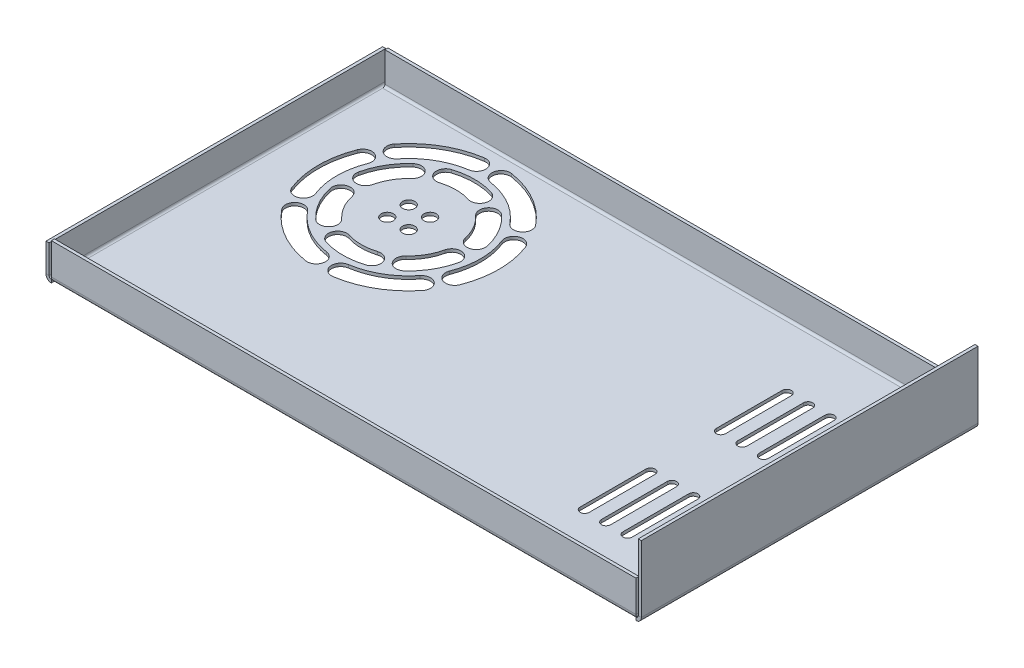
SolidWorks part; units mm, degrees
note: The reader was unsure of these and kept them because the rebuilt part matched: thickness of "Базовая кромка1", "Ребро-кромка1", "Ребро-кромка2", "Ребро-кромка3", "Ребро-кромка4", "Листовой металл3", "Листовой металл4", "Листовой металл5", "Листовой металл6", "Листовой металл7", "Листовой металл8"; flange length of "Ребро-кромка1", "Ребро-кромка2", "Ребро-кромка3", "Ребро-кромка4".
material "6063-O"
ref_plane "Спереди" through (0, 0, 0) normal (0, 0, 1) x (1, 0, 0)
ref_plane "Сверху" through (0, 0, 0) normal (0, 1, 0) x (1, 0, 0)
ref_plane "Справа" through (0, 0, 0) normal (1, 0, 0) x (0, 0, -1)
sketch "Эскиз1" plane through (0, 0, 0) normal (0, 1, 0) x (1, 0, 0)
  line L1 (-97.25, 55) -> (97.25, 55)
  line L2 (-97.25, 55) -> (-97.25, -55)
  line L3 (-97.25, -55) -> (97.25, -55)
  line L4 (97.25, 55) -> (97.25, -55)
  point P4 (0, 55)
  point P6 (-97.25, 0)
  dimension "D1" = 110
  dimension "D2" = 194.5
base flange "Базовая кромка1" sketch "Эскиз1" thickness 1 reverse thickness direction no parameters "D1"=0.7366
edge flange "Ребро-кромка1" sketch "Эскиз8" flange angle 90 flange length 23.5 flange position material inside bend radius 0.7366 thickness 1 relief rectangular parameters "D6"=10
sketch "Эскиз8" plane through (97.25, 0, 0) normal (1, 0, 0) x (0, 0, -1)
  line L0 (-55, 0) -> (55, 0) construction
  line L1 (-55, 0) -> (55, 0)
  line L2 (-55, 0) -> (-55, 22.5)
  line L3 (-55, 22.5) -> (55, 22.5)
  line L4 (55, 22.5) -> (55, 0)
bend "EdgeBend1" bend radius 0.7366 bend angle 90 parameters "D5"=1
edge flange "Ребро-кромка2" sketch "Эскиз11" flange angle 90 flange length 11 flange position material inside bend radius 0.7366 thickness 1 relief rectangular parameters "D6"=10
sketch "Эскиз11" plane through (-97.25, 0, 0) normal (-1, 0, 0) x (0, 0, 1)
  line L0 (-55, 0) -> (55, 0) construction
  line L1 (-55, 0) -> (55, 0)
  line L2 (-55, 0) -> (-55, 10)
  line L3 (-55, 10) -> (55, 10)
  line L4 (55, 10) -> (55, 0)
bend "EdgeBend2" bend radius 0.7366 bend angle 90 parameters "D5"=2
edge flange "Ребро-кромка3" sketch "Эскиз14" flange angle 90 flange length 12 flange position material inside bend radius 0.7366 thickness 1 relief none parameters "D6"=10
sketch "Эскиз14" plane through (0, 0, 55) normal (0, 0, 1) x (1, 0, 0)
  line L0 (-95.5134, 0) -> (95.5134, 0) construction
  line L1 (-95.5134, 0) -> (95.5134, 0)
  line L2 (-95.5134, 0) -> (-95.5134, 11)
  line L3 (-95.5134, 11) -> (95.5134, 11)
  line L4 (95.5134, 11) -> (95.5134, 0)
bend "EdgeBend3" bend radius 0.7366 bend angle 90 parameters "D5"=3
edge flange "Ребро-кромка4" sketch "Эскиз17" flange angle 90 flange length 11.5 flange position material inside bend radius 0.7366 thickness 1 relief none parameters "D6"=10
sketch "Эскиз17" plane through (0, 0, -55) normal (0, 0, -1) x (-1, 0, 0)
  line L0 (-95.5134, 0) -> (95.5134, 0) construction
  line L1 (-95.5134, 0) -> (95.5134, 0)
  line L2 (-95.5134, 0) -> (-95.5134, 10.5)
  line L3 (-95.5134, 10.5) -> (95.5134, 10.5)
  line L4 (95.5134, 10.5) -> (95.5134, 0)
bend "EdgeBend4" bend radius 0.7366 bend angle 90 parameters "D5"=4
sketch "Эскиз18" plane through (0, -1, 0) normal (0, -1, 0) x (1, 0, 0)
  line L0 (-95.5134, 0) -> (95.5134, 0) construction
  line L1 (-95.5134, 53.2634) -> (-95.5134, -53.2634) construction
  line L2 (95.5134, -53.2634) -> (95.5134, 53.2634) construction
  line L3 (84.75, 33) -> (84.75, 11.5) construction
  line L4 (86.25, 33) -> (86.25, 11.5)
  line L5 (83.25, 33) -> (83.25, 11.5)
  line L6 (97.25, -55) -> (97.25, 55) construction
  line L7 (95.5134, 55) -> (-95.5134, 55) construction
  line L8 (84.75, -33) -> (84.75, -11.5) construction
  line L9 (86.25, -33) -> (86.25, -11.5)
  line L10 (83.25, -33) -> (83.25, -11.5)
  line L11 (-102.5134, 0) -> (88.5134, 0) construction
  line L12 (77.75, 33) -> (77.75, 11.5) construction
  line L13 (79.25, 33) -> (79.25, 11.5)
  line L14 (76.25, 33) -> (76.25, 11.5)
  line L15 (77.75, -33) -> (77.75, -11.5) construction
  line L16 (79.25, -33) -> (79.25, -11.5)
  line L17 (76.25, -33) -> (76.25, -11.5)
  line L18 (-109.5134, 0) -> (81.5134, 0) construction
  line L19 (70.75, 33) -> (70.75, 11.5) construction
  line L20 (72.25, 33) -> (72.25, 11.5)
  line L21 (69.25, 33) -> (69.25, 11.5)
  line L22 (70.75, -33) -> (70.75, -11.5) construction
  line L23 (72.25, -33) -> (72.25, -11.5)
  line L24 (69.25, -33) -> (69.25, -11.5)
  line L25 (-116.5134, 0) -> (74.5134, 0) construction
  line L26 (63.75, 33) -> (63.75, 11.5) construction
  line L27 (65.25, 33) -> (65.25, 11.5)
  line L28 (62.25, 33) -> (62.25, 11.5)
  line L29 (63.75, -33) -> (63.75, -11.5) construction
  line L30 (65.25, -33) -> (65.25, -11.5)
  line L31 (62.25, -33) -> (62.25, -11.5)
  line L32 (-123.5134, 0) -> (67.5134, 0) construction
  line L33 (56.75, 33) -> (56.75, 11.5) construction
  line L34 (58.25, 33) -> (58.25, 11.5)
  line L35 (55.25, 33) -> (55.25, 11.5)
  line L36 (56.75, -33) -> (56.75, -11.5) construction
  line L37 (58.25, -33) -> (58.25, -11.5)
  line L38 (55.25, -33) -> (55.25, -11.5)
  line L39 (-79.4367, -30.6341) -> (-54.75, -21) construction
  line L40 (-54.75, -21) -> (-79.4367, -11.3659) construction
  line L41 (-54.75, -21) -> (-81.25, -21) construction
  line L42 (-97.25, 55) -> (-97.25, -55) construction
  line L43 (-95.5134, -55) -> (95.5134, -55) construction
  line L44 (-54.75, -21) -> (-54.75, -39.5) construction
  line L45 (-54.75, -21) -> (-75.4367, -4.4377) construction
  line L46 (-60.3171, -38.6425) -> (-54.75, -21) construction
  line L47 (-54.75, -21) -> (-49.1829, -38.6425) construction
  line L48 (-54.75, -21) -> (-67.2453, -34.6425) construction
  line L49 (-54.75, -21) -> (-70.7715, -30.25) construction
  line L50 (-72.8124, -25) -> (-54.75, -21) construction
  line L51 (-54.75, -21) -> (-67.2453, -34.6425) construction
  line L52 (-54.75, -21) -> (-72.8124, -17) construction
  line L53 (-54.75, -21) -> (-70.7715, -11.75) construction
  line L54 (-67.2453, -7.3575) -> (-54.75, -21) construction
  line L55 (-54.75, -21) -> (-72.8124, -17) construction
  line L56 (-54.75, -21) -> (-60.3171, -3.3575) construction
  line L57 (-54.75, -21) -> (-54.75, -2.5) construction
  line L58 (-49.1829, -3.3575) -> (-54.75, -21) construction
  line L59 (-54.75, -21) -> (-60.3171, -3.3575) construction
  line L60 (-54.75, -21) -> (-42.2547, -7.3575) construction
  line L61 (-54.75, -21) -> (-38.7285, -11.75) construction
  line L62 (-36.6876, -17) -> (-54.75, -21) construction
  line L63 (-54.75, -21) -> (-42.2547, -7.3575) construction
  line L64 (-54.75, -21) -> (-36.6876, -25) construction
  line L65 (-54.75, -21) -> (-38.7285, -30.25) construction
  line L66 (-42.2547, -34.6425) -> (-54.75, -21) construction
  line L67 (-54.75, -21) -> (-36.6876, -25) construction
  line L68 (-54.75, -21) -> (-49.1829, -38.6425) construction
  line L70 (-58.25, -17.5) -> (-51.25, -17.5) construction
  line L71 (-58.25, -17.5) -> (-58.25, -24.5) construction
  line L72 (-58.25, -24.5) -> (-51.25, -24.5) construction
  line L73 (-51.25, -17.5) -> (-51.25, -24.5) construction
  arc A0 (86.25, 33) -> (83.25, 33) centre (84.75, 33) ccw
  arc A1 (83.25, 11.5) -> (86.25, 11.5) centre (84.75, 11.5) ccw
  arc A2 (86.25, -33) -> (83.25, -33) centre (84.75, -33) cw
  arc A3 (83.25, -11.5) -> (86.25, -11.5) centre (84.75, -11.5) cw
  arc A4 (79.25, 33) -> (76.25, 33) centre (77.75, 33) ccw
  arc A5 (76.25, 11.5) -> (79.25, 11.5) centre (77.75, 11.5) ccw
  arc A6 (79.25, -33) -> (76.25, -33) centre (77.75, -33) cw
  arc A7 (76.25, -11.5) -> (79.25, -11.5) centre (77.75, -11.5) cw
  arc A8 (72.25, 33) -> (69.25, 33) centre (70.75, 33) ccw
  arc A9 (69.25, 11.5) -> (72.25, 11.5) centre (70.75, 11.5) ccw
  arc A10 (72.25, -33) -> (69.25, -33) centre (70.75, -33) cw
  arc A11 (69.25, -11.5) -> (72.25, -11.5) centre (70.75, -11.5) cw
  arc A12 (65.25, 33) -> (62.25, 33) centre (63.75, 33) ccw
  arc A13 (62.25, 11.5) -> (65.25, 11.5) centre (63.75, 11.5) ccw
  arc A14 (65.25, -33) -> (62.25, -33) centre (63.75, -33) cw
  arc A15 (62.25, -11.5) -> (65.25, -11.5) centre (63.75, -11.5) cw
  arc A16 (58.25, 33) -> (55.25, 33) centre (56.75, 33) ccw
  arc A17 (55.25, 11.5) -> (58.25, 11.5) centre (56.75, 11.5) ccw
  arc A18 (58.25, -33) -> (55.25, -33) centre (56.75, -33) cw
  arc A19 (55.25, -11.5) -> (58.25, -11.5) centre (56.75, -11.5) cw
  arc A20 (-79.4367, -30.6341) -> (-79.4367, -11.3659) centre (-54.75, -21) cw construction
  arc A21 (-82.2314, -10.2753) -> (-82.2314, -31.7247) centre (-54.75, -21) ccw
  arc A22 (-76.642, -12.4566) -> (-76.642, -29.5434) centre (-54.75, -21) ccw
  arc A23 (-82.2314, -10.2753) -> (-76.642, -12.4566) centre (-79.4367, -11.3659) cw
  arc A24 (-82.2314, -31.7247) -> (-76.642, -29.5434) centre (-79.4367, -30.6341) ccw
  arc A25 (-60.3171, -38.6425) -> (-49.1829, -38.6425) centre (-54.75, -21) ccw construction
  arc A26 (-61.2199, -41.5034) -> (-48.2801, -41.5034) centre (-54.75, -21) ccw
  arc A27 (-59.4143, -35.7815) -> (-50.0857, -35.7815) centre (-54.75, -21) ccw
  arc A28 (-61.2199, -41.5034) -> (-59.4143, -35.7815) centre (-60.3171, -38.6425) cw
  arc A29 (-50.0857, -35.7815) -> (-48.2801, -41.5034) centre (-49.1829, -38.6425) cw
  arc A30 (-59.2028, 8.162) -> (-77.7786, -2.5627) centre (-54.75, -21) ccw
  arc A31 (-58.2972, 2.2307) -> (-73.0948, -6.3127) centre (-54.75, -21) ccw
  arc A32 (-59.2028, 8.162) -> (-58.2972, 2.2307) centre (-58.75, 5.1964) cw
  arc A33 (-77.7786, -2.5627) -> (-73.0948, -6.3127) centre (-75.4367, -4.4377) ccw
  arc A34 (-75.4367, -4.4377) -> (-58.75, 5.1964) centre (-54.75, -21) cw construction
  arc A35 (-75.7414, -25.6486) -> (-69.2716, -36.8548) centre (-54.75, -21) ccw
  arc A36 (-69.8834, -24.3514) -> (-65.219, -32.4302) centre (-54.75, -21) ccw
  arc A37 (-75.7414, -25.6486) -> (-69.8834, -24.3514) centre (-72.8124, -25) cw
  arc A38 (-65.219, -32.4302) -> (-69.2716, -36.8548) centre (-67.2453, -34.6425) cw
  arc A39 (-72.8124, -25) -> (-67.2453, -34.6425) centre (-54.75, -21) ccw construction
  arc A40 (-31.7214, -2.5627) -> (-50.2972, 8.162) centre (-54.75, -21) ccw
  arc A41 (-36.4052, -6.3127) -> (-51.2028, 2.2307) centre (-54.75, -21) ccw
  arc A42 (-31.7214, -2.5627) -> (-36.4052, -6.3127) centre (-34.0633, -4.4377) cw
  arc A43 (-50.2972, 8.162) -> (-51.2028, 2.2307) centre (-50.75, 5.1964) ccw
  arc A44 (-50.75, 5.1964) -> (-34.0633, -4.4377) centre (-54.75, -21) cw construction
  arc A45 (-69.2716, -5.1452) -> (-75.7414, -16.3514) centre (-54.75, -21) ccw
  arc A46 (-65.219, -9.5698) -> (-69.8834, -17.6486) centre (-54.75, -21) ccw
  arc A47 (-69.2716, -5.1452) -> (-65.219, -9.5698) centre (-67.2453, -7.3575) cw
  arc A48 (-69.8834, -17.6486) -> (-75.7414, -16.3514) centre (-72.8124, -17) cw
  arc A49 (-67.2453, -7.3575) -> (-72.8124, -17) centre (-54.75, -21) ccw construction
  arc A50 (-27.2686, -31.7247) -> (-27.2686, -10.2753) centre (-54.75, -21) ccw
  arc A51 (-32.858, -29.5434) -> (-32.858, -12.4566) centre (-54.75, -21) ccw
  arc A52 (-27.2686, -31.7247) -> (-32.858, -29.5434) centre (-30.0633, -30.6341) cw
  arc A53 (-27.2686, -10.2753) -> (-32.858, -12.4566) centre (-30.0633, -11.3659) ccw
  arc A54 (-30.0633, -11.3659) -> (-30.0633, -30.6341) centre (-54.75, -21) cw construction
  arc A55 (-48.2801, -0.4966) -> (-61.2199, -0.4966) centre (-54.75, -21) ccw
  arc A56 (-50.0857, -6.2185) -> (-59.4143, -6.2185) centre (-54.75, -21) ccw
  arc A57 (-48.2801, -0.4966) -> (-50.0857, -6.2185) centre (-49.1829, -3.3575) cw
  arc A58 (-59.4143, -6.2185) -> (-61.2199, -0.4966) centre (-60.3171, -3.3575) cw
  arc A59 (-49.1829, -3.3575) -> (-60.3171, -3.3575) centre (-54.75, -21) ccw construction
  arc A60 (-50.2972, -50.162) -> (-31.7214, -39.4373) centre (-54.75, -21) ccw
  arc A61 (-51.2028, -44.2307) -> (-36.4052, -35.6873) centre (-54.75, -21) ccw
  arc A62 (-50.2972, -50.162) -> (-51.2028, -44.2307) centre (-50.75, -47.1964) cw
  arc A63 (-31.7214, -39.4373) -> (-36.4052, -35.6873) centre (-34.0633, -37.5623) ccw
  arc A64 (-34.0633, -37.5623) -> (-50.75, -47.1964) centre (-54.75, -21) cw construction
  arc A65 (-33.7586, -16.3514) -> (-40.2284, -5.1452) centre (-54.75, -21) ccw
  arc A66 (-39.6166, -17.6486) -> (-44.281, -9.5698) centre (-54.75, -21) ccw
  arc A67 (-33.7586, -16.3514) -> (-39.6166, -17.6486) centre (-36.6876, -17) cw
  arc A68 (-44.281, -9.5698) -> (-40.2284, -5.1452) centre (-42.2547, -7.3575) cw
  arc A69 (-36.6876, -17) -> (-42.2547, -7.3575) centre (-54.75, -21) ccw construction
  arc A70 (-77.7786, -39.4373) -> (-59.2028, -50.162) centre (-54.75, -21) ccw
  arc A71 (-73.0948, -35.6873) -> (-58.2972, -44.2307) centre (-54.75, -21) ccw
  arc A72 (-77.7786, -39.4373) -> (-73.0948, -35.6873) centre (-75.4367, -37.5623) cw
  arc A73 (-59.2028, -50.162) -> (-58.2972, -44.2307) centre (-58.75, -47.1964) ccw
  arc A74 (-58.75, -47.1964) -> (-75.4367, -37.5623) centre (-54.75, -21) cw construction
  arc A75 (-40.2284, -36.8548) -> (-33.7586, -25.6486) centre (-54.75, -21) ccw
  arc A76 (-44.281, -32.4302) -> (-39.6166, -24.3514) centre (-54.75, -21) ccw
  arc A77 (-40.2284, -36.8548) -> (-44.281, -32.4302) centre (-42.2547, -34.6425) cw
  arc A78 (-39.6166, -24.3514) -> (-33.7586, -25.6486) centre (-36.6876, -25) cw
  arc A79 (-42.2547, -34.6425) -> (-36.6876, -25) centre (-54.75, -21) ccw construction
  circle A80 centre (-58.25, -17.5) radius 2
  circle A81 centre (-51.25, -17.5) radius 2
  circle A82 centre (-51.25, -24.5) radius 2
  circle A83 centre (-58.25, -24.5) radius 2
  point P8 (84.75, 22.25)
  point P15 (84.75, 10)
  point P16 (84.75, 34.5)
  point P21 (84.75, -22.25)
  point P31 (77.75, 22.25)
  point P38 (77.75, -22.25)
  point P47 (70.75, 22.25)
  point P54 (70.75, -22.25)
  point P63 (63.75, 22.25)
  point P70 (63.75, -22.25)
  point P79 (56.75, 22.25)
  point P86 (56.75, -22.25)
  point P94 (-81.25, -21)
  point P110 (-54.75, -39.5)
  point P185 (-54.75, -21)
  point P193 (-51.25, -21)
  point P194 (-54.75, -24.5)
  dimension "D1" = 1.5
  dimension "D9" = 15.5
  dimension "D11" = 3
  dimension "D10" = 23.5
  dimension "D12" = 3
  dimension "D13" = 60
  dimension "D17" = 4
  dimension "D2" = 11
  dimension "D3" = 10
  dimension "D4" = 20.5
  dimension "D6" = 39
  dimension "D7" = 42.5
  dimension "D8" = 34
  dimension "D14" = 8
  dimension "D15" = 60
  dimension "D16" = 8
  dimension "D18" = 7
  dimension "D5" = 5
extrude "Вырез-Вытянуть1" cut sketch "Эскиз18" against normal through all normal cut yes
sketch "Сгиб-Линии1" [suppressed] plane through (0, 0, 0) normal (0, 1, 0) x (1, 0, 0)
sketch "Граничная рамка1" [suppressed] plane through (0, 0, 0) normal (0, 1, 0) x (1, 0, 0)
sheet metal parameters "Листовой металл3" thickness 1 parameters "D1"=0.7366
flat pattern "Развертка3" [suppressed]
sketch "Сгиб-Линии2" plane through (0, 0, 0) normal (0, 1, 0) x (1, 0, 0)
sketch "Граничная рамка2" [suppressed] plane through (0, 0, 0) normal (0, 1, 0) x (1, 0, 0)
sheet metal parameters "Листовой металл4" thickness 1 parameters "D1"=0.7366
flat pattern "Развертка3" [suppressed]
sketch "Сгиб-Линии2" plane through (0, 0, 0) normal (0, 1, 0) x (1, 0, 0)
sketch "Граничная рамка2" [suppressed] plane through (0, 0, 0) normal (0, 1, 0) x (1, 0, 0)
bend of the flat pattern "Плоское состояние-<EdgeBend1>1"
sheet metal parameters "Листовой металл5" thickness 1 parameters "D1"=0.7366
flat pattern "Развертка3" [suppressed]
sketch "Сгиб-Линии2" plane through (0, 0, 0) normal (0, 1, 0) x (1, 0, 0)
sketch "Граничная рамка2" [suppressed] plane through (0, 0, 0) normal (0, 1, 0) x (1, 0, 0)
bend of the flat pattern "Плоское состояние-<EdgeBend1>1"
bend of the flat pattern "Плоское состояние-<EdgeBend2>1"
sheet metal parameters "Листовой металл6" thickness 1 parameters "D1"=0.7366
flat pattern "Развертка3" [suppressed]
sketch "Сгиб-Линии2" plane through (0, 0, 0) normal (0, 1, 0) x (1, 0, 0)
sketch "Граничная рамка2" [suppressed] plane through (0, 0, 0) normal (0, 1, 0) x (1, 0, 0)
bend of the flat pattern "Плоское состояние-<EdgeBend1>1"
bend of the flat pattern "Плоское состояние-<EdgeBend2>1"
bend of the flat pattern "Плоское состояние-<EdgeBend3>1"
sheet metal parameters "Листовой металл7" thickness 1 parameters "D1"=0.7366
flat pattern "Развертка3" [suppressed]
sketch "Сгиб-Линии2" plane through (0, 0, 0) normal (0, 1, 0) x (1, 0, 0)
sketch "Граничная рамка2" [suppressed] plane through (0, 0, 0) normal (0, 1, 0) x (1, 0, 0)
bend of the flat pattern "Плоское состояние-<EdgeBend1>1"
bend of the flat pattern "Плоское состояние-<EdgeBend2>1"
bend of the flat pattern "Плоское состояние-<EdgeBend3>1"
bend of the flat pattern "Плоское состояние-<EdgeBend4>1"
sheet metal parameters "Листовой металл8" thickness 1 parameters "D1"=0.7366
flat pattern "Развертка3"
sketch "Сгиб-Линии2" plane through (0, 0, 0) normal (0, 1, 0) x (1, 0, 0)
  line L0 (95.5134, 54.2346) -> (-95.5134, 54.2346) construction
  line L1 (-95.5134, -54.2346) -> (95.5134, -54.2346) construction
  line L2 (-96.4846, 55) -> (-96.4846, -55) construction
  line L3 (96.4846, -55) -> (96.4846, 55) construction
  line L4 (95.5134, 54.2346) -> (-95.5134, 54.2346) construction
  line L5 (-95.5134, -54.2346) -> (95.5134, -54.2346) construction
  line L6 (-96.4846, 55) -> (-96.4846, -55) construction
  line L7 (96.4846, -55) -> (96.4846, 55) construction
sketch3d "Граничная рамка2" [suppressed]
  line L0 (119.2192, -65.4692, 0) -> (-106.7192, -65.4692, 0) construction
  line L1 (119.2192, 64.9692, 0) -> (-106.7192, 64.9692, 0) construction
  line L2 (119.2192, -65.4692, 0) -> (119.2192, 64.9692, 0) construction
  line L3 (-106.7192, -65.4692, 0) -> (-106.7192, 64.9692, 0) construction
bend of the flat pattern "Плоское состояние-<EdgeBend1>1"
bend of the flat pattern "Плоское состояние-<EdgeBend2>1"
bend of the flat pattern "Плоское состояние-<EdgeBend3>1"
bend of the flat pattern "Плоское состояние-<EdgeBend4>1"
